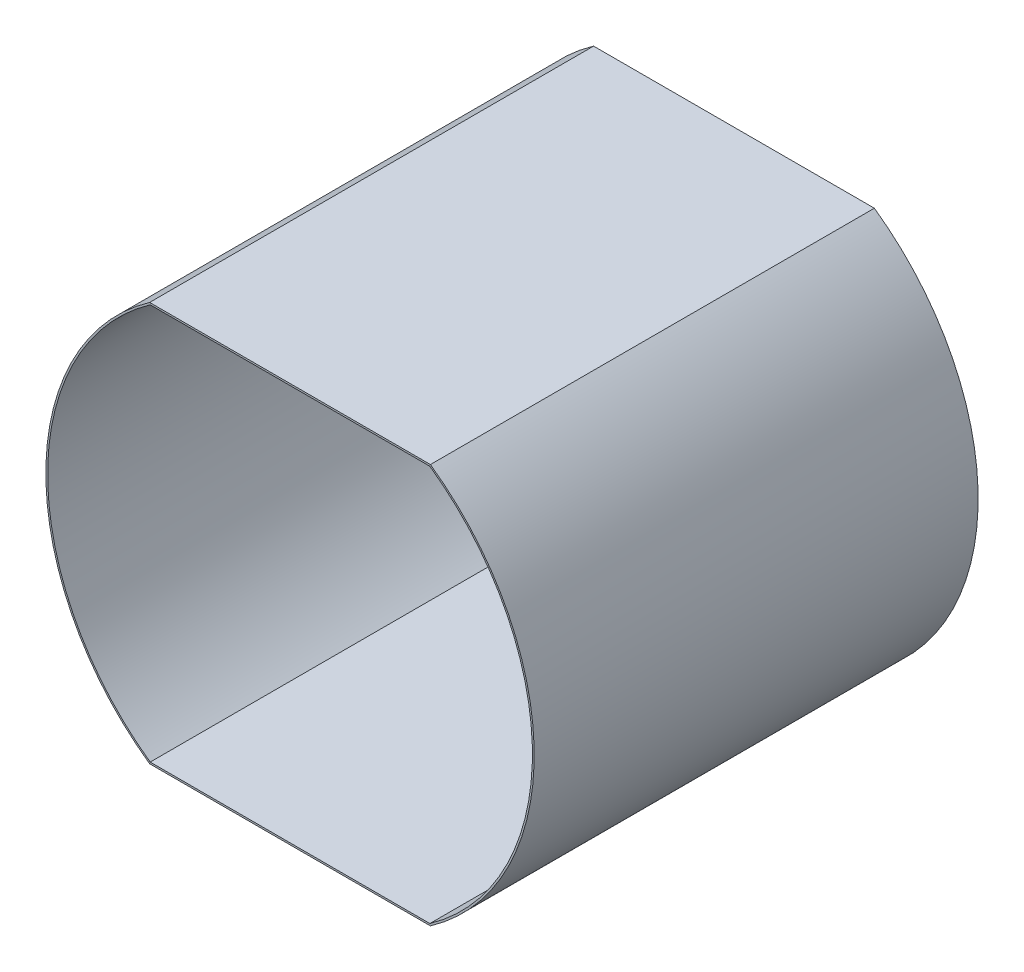
SolidWorks part; units mm, degrees
ref_plane "Front Plane" through (0, 0, 0) normal (0, 0, 1) x (1, 0, 0)
ref_plane "Top Plane" through (0, 0, 0) normal (0, 1, 0) x (1, 0, 0)
ref_plane "Right Plane" through (0, 0, 0) normal (1, 0, 0) x (0, 0, -1)
sketch "Sketch2" plane through (0, 0, 0) normal (0, 0, 1) x (1, 0, 0)
  line L3 (15.8114, 22.5) -> (-15.8114, 22.5)
  line L5 (15.8114, -22.5) -> (-15.8114, -22.5)
  arc A1 (15.8114, -22.5) -> (15.8114, 22.5) centre (0, 0) ccw
  arc A2 (-15.8114, 22.5) -> (-15.8114, -22.5) centre (0, 0) ccw
  circle A3 centre (0, 0) radius 2
extrude "Boss-Extrude8" add sketch "Sketch2" along normal blind 50
shell "Shell4" thickness 0.2 removed face at (2, 0, 50) removed face at (0, 0, 50)
